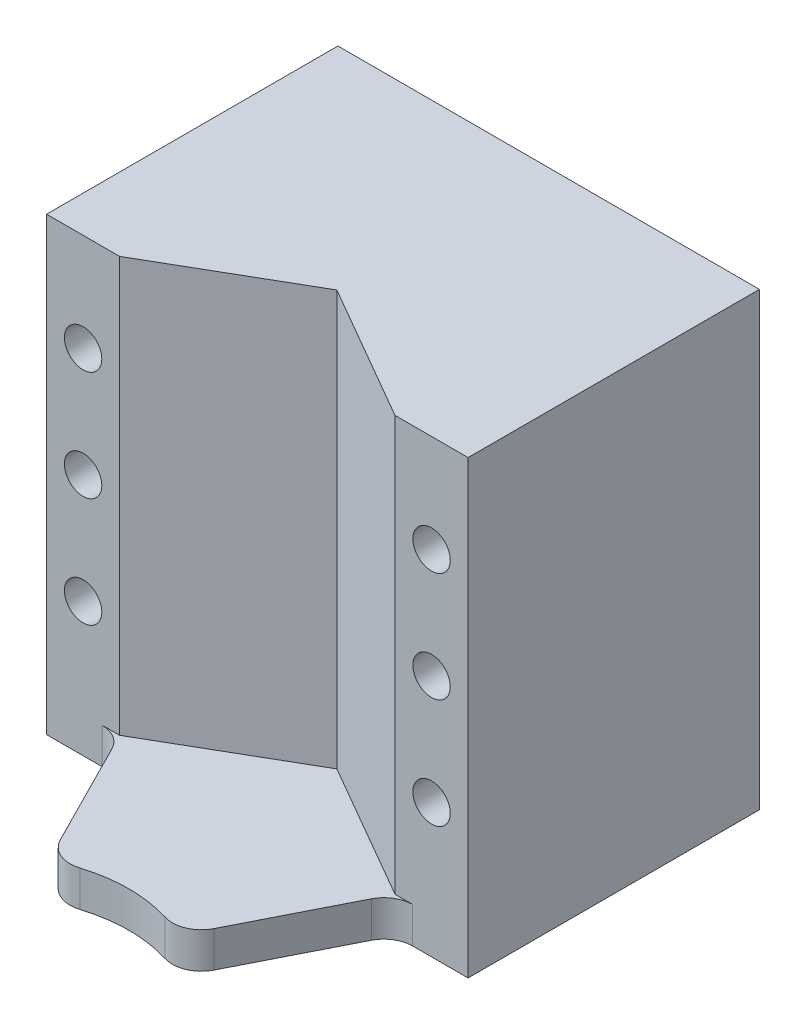
SolidWorks part; units mm, degrees
ref_plane "Front Plane" through (0, 0, 0) normal (0, 0, 1) x (1, 0, 0)
ref_plane "Top Plane" through (0, 0, 0) normal (0, 1, 0) x (1, 0, 0)
ref_plane "Right Plane" through (0, 0, 0) normal (1, 0, 0) x (0, 0, -1)
sketch "Sketch1" plane through (0, 0, 0) normal (0, 1, 0) x (1, 0, 0)
  line L0 (0, 0) -> (47.8912, -27.65)
  line L1 (47.8912, -27.65) -> (73.3, -27.65)
  line L2 (73.3, -27.65) -> (73.3, 73.6729)
  line L3 (73.3, 73.6729) -> (-73.3, 73.6729)
  line L4 (-73.3, 73.6729) -> (-73.3, -27.65)
  line L5 (-73.3, -27.65) -> (-47.8912, -27.65)
  line L6 (-47.8912, -27.65) -> (0, 0)
  line L7 (-18.9998, 73.6729) -> (19, 73.6729) construction
  line L8 (0, 0) -> (-30, -17.3205) construction
  line L9 (-30, -17.3205) -> (-30, -51.9615) construction
  line L10 (-30, -51.9615) -> (0, -69.282) construction
  line L11 (0, -69.282) -> (30, -51.9615) construction
  line L12 (30, -51.9615) -> (30, -17.3205) construction
  line L13 (30, -17.3205) -> (0, 0) construction
  circle A0 centre (0, -34.641) radius 30 construction
  dimension "D4" = 60
  dimension "D2" = 55.3
  dimension "D3" = 146.6
extrude "Boss-Extrude1" add sketch "Sketch1" along normal blind 144.25
sketch "Sketch3" plane through (0, 0, 0) normal (0, -1, 0) x (1, 0, 0)
  line L0 (-47.8912, 27.65) -> (-22.5815, 77.65)
  line L1 (22.5815, 77.65) -> (47.8912, 27.65)
  line L15 (-47.8912, 27.65) -> (-73.3, 27.65)
  line L16 (-73.3, 27.65) -> (-73.3, -73.6729)
  line L17 (-73.3, -73.6729) -> (73.3, -73.6729)
  line L18 (73.3, -73.6729) -> (73.3, 27.65)
  line L19 (73.3, 27.65) -> (47.8912, 27.65)
  arc A0 (-22.5815, 77.65) -> (22.5815, 77.65) centre (0, 122.2603) ccw
  dimension "D3" = 50
  dimension "D2" = 50
extrude "Boss-Extrude2" add sketch "Sketch3" along normal blind 12.5
fillet "Fillet1" radius 10 4 edges at (47.8912, -6.25, 27.65) (22.5815, -6.25, 77.65) (-22.5815, -6.25, 77.65) (-47.8912, -6.25, 27.65)
sketch "Sketch7" plane through (0, 0, 27.65) normal (0, 0, 1) x (1, 0, 0)
  point P0 (-60.5951, 110.2261)
  point P3 (-60.5951, 72.1261)
  point P6 (-60.5951, 34.0261)
  point P9 (60.6, 110.2261)
  point P12 (60.6, 72.1261)
  point P15 (60.6, 34.0261)
hole_wizard "M12 Clearance Hole1" positions "Sketch7" profile "Sketch6" hole size "M12" standard "ANSI Metric" end condition through all
sketch "Sketch6" plane through (-60.5951, 110.2261, 27.65) normal (1, 0, 0) x (0, -1, 0)
  line L0 (0, 0) -> (0, 101.3229)
  line L1 (0, 101.3229) -> (6.5, 101.3229)
  line L2 (6.5, 101.3229) -> (6.5, 0)
  line L5 (6.5, 0) -> (0, 0)
  line L11 (0, -6.35) -> (0, 107.95) construction
  dimension "Thru Hole Dia." = 13
  dimension "Thru Hole Depth" = 101.3229
sketch "Sketch8" plane through (0, -12.5, 0) normal (0, -1, 0) x (1, 0, 0)
  line L0 (-73.3, -73.6729) -> (73.3, -73.6729) construction
  line L1 (-44.5, -33.6729) -> (44.5, -33.6729)
  line L2 (-44.5, -33.6729) -> (-44.5, -73.6729)
  line L3 (-44.5, -73.6729) -> (44.5, -73.6729)
  line L4 (44.5, -33.6729) -> (44.5, -73.6729)
  point P4 (0, -33.6729)
  point P6 (-44.5, -73.6729)
  dimension "D1" = 89
  dimension "D2" = 40
extrude "Cut-Extrude1" cut sketch "Sketch8" against normal offset from surface 10 and the other way through all up to face at (0, 144.25, -5.2494)
